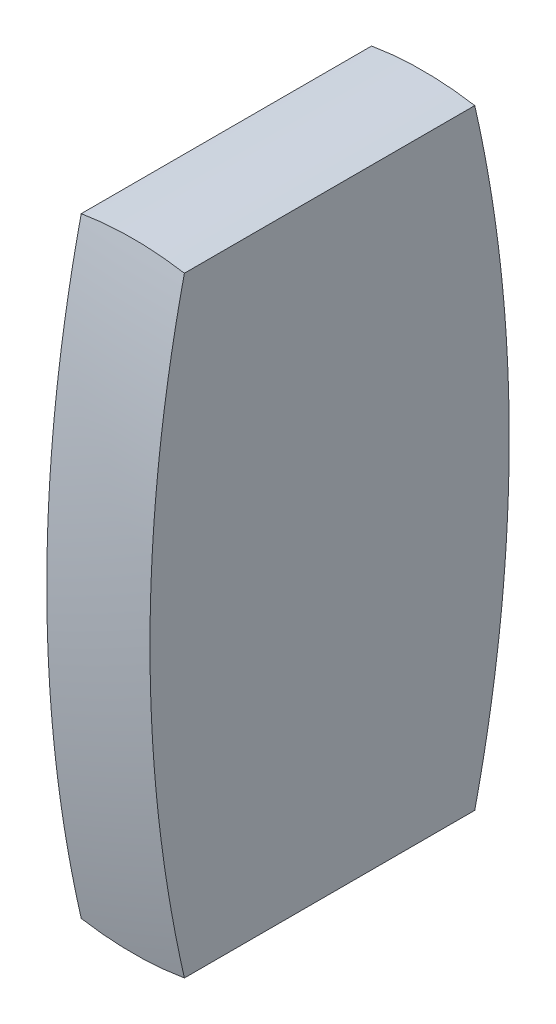
SolidWorks part; units mm, degrees
ref_plane "Front Plane" through (0, 0, 0) normal (0, 0, 1) x (1, 0, 0)
ref_plane "Top Plane" through (0, 0, 0) normal (0, 1, 0) x (1, 0, 0)
ref_plane "Right Plane" through (0, 0, 0) normal (1, 0, 0) x (0, 0, -1)
sketch "Sketch1" plane through (0, 0, 0) normal (0, 0, 1) x (1, 0, 0)
  circle A0 centre (0, 0) radius 3
extrude "Boss-Extrude1" add sketch "Sketch1" along normal blind 10 and the other way blind 10
sketch "Sketch5" plane through (0, 0, 0) normal (0, 1, 0) x (1, 0, 0)
  arc A0 (0, -1.75) -> (0, 24.85) centre (0, 11.55) cw construction
sketch "Sketch7" plane through (0, 0, 0) normal (0, 1, 0) x (1, 0, 0)
  line L0 (-5.3502, -0.6264) -> (-7.837, -11.63)
  line L1 (-7.837, -11.63) -> (0, -12.6817)
  line L2 (0, -12.6817) -> (0, -1.75)
  arc A1 (0, -1.75) -> (-5.3502, -0.6264) centre (0, 11.55) cw
revolve "Cut-Revolve5" cut sketch "Sketch7" angle 360 about axis through (0, 0, -10) along (0, 0, 1)
sketch "Sketch9" plane through (0, 0, 0) normal (0, 1, 0) x (1, 0, 0)
  arc A0 (0, -24.85) -> (0, 1.75) centre (0, -11.55) cw construction
sketch "Sketch10" plane through (0, 0, 0) normal (0, 1, 0) x (1, 0, 0)
  line L1 (-9.335, -2.0765) -> (-9.335, 13.2203)
  line L2 (-9.335, 13.2203) -> (0, 13.2203)
  line L3 (0, 13.2203) -> (0, 1.75)
  arc A1 (0, 1.75) -> (-9.335, -2.0765) centre (0, -11.55) ccw
revolve "Cut-Revolve6" cut sketch "Sketch10" angle 360 about L3
sketch "Sketch11" plane through (0, 0, 0) normal (0, 0, 1) x (1, 0, 0)
  line L1 (0.5, -3.3452) -> (-0.5, -3.3452)
  line L2 (0.5, -3.3452) -> (0.5, 3.3452)
  line L3 (0.5, 3.3452) -> (-0.5, 3.3452)
  line L4 (-0.5, -3.3452) -> (-0.5, 3.3452)
  line L5 (0.5, -3.3452) -> (-0.5, 3.3452) construction
  line L6 (0.5, 3.3452) -> (-0.5, -3.3452) construction
  point P0 (0, 0)
extrude "Cut-Extrude1" cut sketch "Sketch11" against normal blind 10 and the other way blind 10 flip side to cut
equation "\"R\"= 0.0132m"
equation "\"w\"= 0.00366m"
